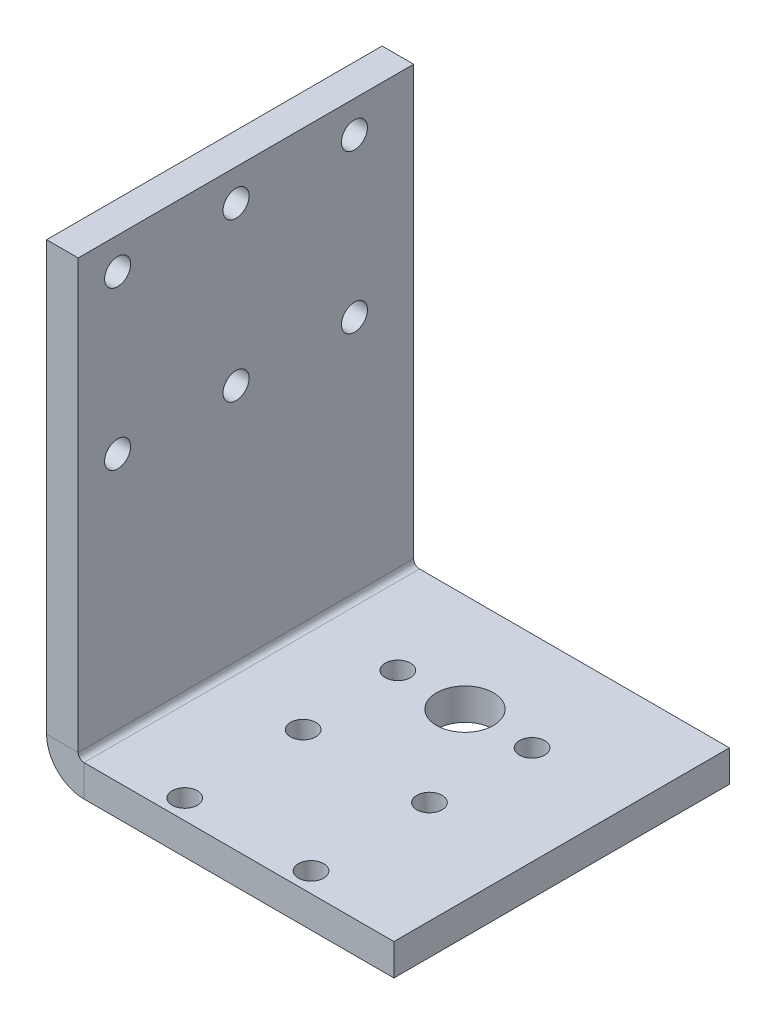
SolidWorks part; units mm, degrees
note: The reader was unsure of these and kept them because the rebuilt part matched: thickness of "基材-凸緣2", "鈑金4", "鈑金6", "鈑金7", "鈑金9", "鈑金12", "鈑金16"; bend radius of "基材彎折1".
material "AISI 304"
ref_plane "前基準面" through (0, 0, 0) normal (0, 0, 1) x (1, 0, 0)
ref_plane "上基準面" through (0, 0, 0) normal (0, 1, 0) x (1, 0, 0)
ref_plane "右基準面" through (0, 0, 0) normal (1, 0, 0) x (0, 0, -1)
sketch "草圖16" plane through (0, 0, 0) normal (0, 0, 1) x (1, 0, 0)
  line L0 (0, 0) -> (0, 55)
  line L1 (0, 0) -> (40, 0)
  dimension "D1" = 40
  dimension "D2" = 55
base flange "基材-凸緣2" sketch "草圖16" end condition mid plane depth 42.5 reverse direction no thickness 4 reverse thickness direction no bend radius 0.7366
bend "基材彎折1" bend radius 0.7366 bend angle 90 parameters "D5"=1
hole_wizard "M3 餘隙孔1" positions "草圖22" profile "草圖23" hole size "M3" standard "Ansi Metric" end condition through all
sketch "草圖22" plane through (0, 0, 0) normal (0, -1, 0) x (-1, 0, 0)
  line L1 (-11, -3.75) -> (-27, -3.75) construction
  line L2 (-11, -3.75) -> (-11, -18.75) construction
  line L3 (-11, -18.75) -> (-27, -18.75) construction
  line L4 (-27, -3.75) -> (-27, -18.75) construction
  line L5 (-11, -3.75) -> (-27, -18.75) construction
  line L6 (-11, -18.75) -> (-27, -3.75) construction
  line L11 (4, -21.25) -> (4, 21.25) construction
  line L13 (-0.7366, -21.25) -> (-40, -21.25) construction
  point P2 (-27, -18.75)
  point P57 (-11, -3.75)
  point P58 (-11, -18.75)
  point P59 (-27, -3.75)
  point P95 (-19, -11.25)
  dimension "D1" = 16
  dimension "D2" = 15
  dimension "D3" = 10
  dimension "D4" = 15
sketch "草圖23" plane through (27, 0, 18.75) normal (1, 0, 0) x (0, 0, 1)
  line L0 (0, 0) -> (0, 4)
  line L1 (0, 4) -> (1.6, 4)
  line L2 (1.6, 4) -> (1.6, 0)
  line L5 (1.6, 0) -> (0, 0)
  line L11 (0, -6.35) -> (0, 107.95) construction
  dimension "砮 ふ 畖" = 3.2
  dimension "砮 ふ瞏 " = 4
sketch "草圖24" plane through (0, -4, 0) normal (0, -1, 0) x (1, 0, 0)
  line L0 (19, 11.25) -> (19, -8.75) construction
  line L1 (11, 18.75) -> (27, 18.75) construction
  line L2 (11, 18.75) -> (11, 3.75) construction
  line L3 (11, 3.75) -> (27, 3.75) construction
  line L4 (27, 18.75) -> (27, 3.75) construction
  line L5 (11, 18.75) -> (27, 3.75) construction
  line L6 (11, 3.75) -> (27, 18.75) construction
  circle A0 centre (19, -8.75) radius 3.6
  point P4 (19, 11.25)
  point P13 (19, -8.75)
  dimension "D1" = 7.2
  dimension "D2" = 20
extrude "除料-伸長2" cut sketch "草圖24" against normal through all normal cut yes
hole_wizard "M4x0.7 螺紋孔1" positions "草圖27" profile "草圖28" tap size "M4x0.7" standard "Ansi Metric" end condition through all
sketch "草圖27" plane through (0, 0, 0) normal (-1, 0, 0) x (0, 0, 1)
  line L2 (16.25, 51) -> (16.25, 31) construction
  line L13 (21.25, 55) -> (-21.25, 55) construction
  line L14 (21.25, 55) -> (21.25, 0.7366) construction
  point P104 (16.25, 51)
  point P105 (16.25, 31)
  dimension "D1" = 20
  dimension "D2" = 4
  dimension "D3" = 5
  dimension "D4" = 14
sketch "草圖28" plane through (0, 51, 16.25) normal (0, 1, 0) x (0, 0, -1)
  line L0 (0, 0) -> (0, 4)
  line L1 (0, 4) -> (1.65, 4)
  line L2 (1.65, 4) -> (1.65, 0)
  line L5 (1.65, 0) -> (0, 0)
  line L11 (0, -6.35) -> (0, 107.95) construction
  dimension "貫穿螺孔鑽直徑" = 3.3
  dimension "貫穿螺孔鑽深度" = 4
hole_wizard "M3 餘隙孔2" positions "草圖29" profile "草圖31" hole size "M3" standard "Ansi Metric" end condition through all
sketch "草圖29" plane through (0, -4, 0) normal (0, -1, 0) x (-1, 0, 0)
  line L12 (-19, 8.75) -> (-10.5, 8.75) construction
  circle A0 centre (-19, 8.75) radius 3.6 construction
  point P53 (-10.5, 8.75)
  point P60 (-27.5, 8.75)
  dimension "D1" = 8.5
  dimension "D2" = 17
  dimension "D3" = 60
  dimension "D4" = 60
sketch "草圖31" plane through (27.5, -4, -8.75) normal (1, 0, 0) x (0, 0, -1)
  line L0 (0, 0) -> (0, 59)
  line L1 (0, 59) -> (1.6, 59)
  line L2 (1.6, 59) -> (1.6, 0)
  line L5 (1.6, 0) -> (0, 0)
  line L11 (0, -6.35) -> (0, 107.95) construction
  dimension "貫穿孔直徑" = 3.2
  dimension "貫穿孔深度" = 59
pattern_linear "直線複製排列1" count 3 spacing 15 along (0, 0, -1) of "M4x0.7 螺紋孔1"
sketch "彎折-線3" [suppressed] plane through (0, 0, 0) normal (0, 1, 0) x (1, 0, 0)
sketch "邊界方塊3" [suppressed] plane through (0, 0, 0) normal (0, 1, 0) x (1, 0, 0)
sheet metal parameters "鈑金4" thickness 4 parameters "D1"=0.7366
flat pattern "平板-型式4" [suppressed]
sketch "彎折-線4" plane through (0, 0, 0) normal (0, 1, 0) x (1, 0, 0)
  line L0 (-1.4127, -20) -> (-1.4127, 20) construction
  line L1 (-1.4127, -20) -> (-1.4127, 20) construction
sketch3d "邊界方塊4" [suppressed]
  line L0 (60, 0, 0) -> (-32.8254, 0, 0) construction
  line L1 (60, 40, 0) -> (-32.8254, 40, 0) construction
  line L2 (60, 0, 0) -> (60, 40, 0) construction
  line L3 (-32.8254, 0, 0) -> (-32.8254, 40, 0) construction
bend of the flat pattern "平板-<基材彎折1>1"
sheet metal parameters "鈑金6" thickness 4 parameters "D1"=0.7366
flat pattern "平板-型式4"
sketch "彎折-線4" plane through (0, 0, 0) normal (0, 1, 0) x (1, 0, 0)
  line L0 (-1.4127, -20) -> (-1.4127, 20) construction
  line L1 (-1.4127, -20) -> (-1.4127, 20) construction
sketch3d "邊界方塊4" [suppressed]
  line L0 (40, 0, 0) -> (-42.8254, 0, 0) construction
  line L1 (40, 40, 0) -> (-42.8254, 40, 0) construction
  line L2 (40, 0, 0) -> (40, 40, 0) construction
  line L3 (-42.8254, 0, 0) -> (-42.8254, 40, 0) construction
bend of the flat pattern "平板-<基材彎折1>1"
sheet metal parameters "鈑金7" thickness 4 parameters "D1"=0.7366
flat pattern "平板-型式4"
sketch "彎折-線4" plane through (0, 0, 0) normal (0, 1, 0) x (1, 0, 0)
  line L0 (-1.4127, -20) -> (-1.4127, 20) construction
  line L1 (-1.4127, -20) -> (-1.4127, 20) construction
sketch3d "邊界方塊4" [suppressed]
  line L0 (40, 0, 0) -> (-42.8254, 0, 0) construction
  line L1 (40, 40, 0) -> (-42.8254, 40, 0) construction
  line L2 (40, 0, 0) -> (40, 40, 0) construction
  line L3 (-42.8254, 0, 0) -> (-42.8254, 40, 0) construction
bend of the flat pattern "平板-<基材彎折1>1"
sheet metal parameters "鈑金9" thickness 4 parameters "D1"=0.7366
flat pattern "平板-型式4"
sketch "彎折-線4" plane through (0, 0, 0) normal (0, 1, 0) x (1, 0, 0)
  line L0 (-1.02, -30) -> (-1.02, 30) construction
  line L1 (-1.02, -30) -> (-1.02, 30) construction
sketch3d "邊界方塊4" [suppressed]
  line L0 (40, 0, 0) -> (-52.04, 0, 0) construction
  line L1 (40, 60, 0) -> (-52.04, 60, 0) construction
  line L2 (40, 0, 0) -> (40, 60, 0) construction
  line L3 (-52.04, 0, 0) -> (-52.04, 60, 0) construction
bend of the flat pattern "平板-<基材彎折1>1"
sheet metal parameters "鈑金12" thickness 4 parameters "D1"=0.7366
flat pattern "平板-型式4"
sketch "彎折-線4" plane through (0, 0, 0) normal (0, 1, 0) x (1, 0, 0)
  line L0 (-1.4127, -21.25) -> (-1.4127, 21.25) construction
  line L1 (-1.4127, -21.25) -> (-1.4127, 21.25) construction
sketch3d "邊界方塊4" [suppressed]
  line L0 (40, 0, 0) -> (-57.8254, 0, 0) construction
  line L1 (40, 42.5, 0) -> (-57.8254, 42.5, 0) construction
  line L2 (40, 0, 0) -> (40, 42.5, 0) construction
  line L3 (-57.8254, 0, 0) -> (-57.8254, 42.5, 0) construction
bend of the flat pattern "平板-<基材彎折1>1"
sheet metal parameters "鈑金16" thickness 4 parameters "D1"=0.7366
flat pattern "平板-型式4"
sketch "彎折-線4" plane through (0, 0, 0) normal (0, 1, 0) x (1, 0, 0)
  line L0 (-1.4127, -21.25) -> (-1.4127, 21.25) construction
  line L1 (-1.4127, -21.25) -> (-1.4127, 21.25) construction
sketch3d "邊界方塊4" [suppressed]
  line L0 (40, 0, 0) -> (-57.8254, 0, 0) construction
  line L1 (40, 42.5, 0) -> (-57.8254, 42.5, 0) construction
  line L2 (40, 0, 0) -> (40, 42.5, 0) construction
  line L3 (-57.8254, 0, 0) -> (-57.8254, 42.5, 0) construction
bend of the flat pattern "平板-<基材彎折1>1"
